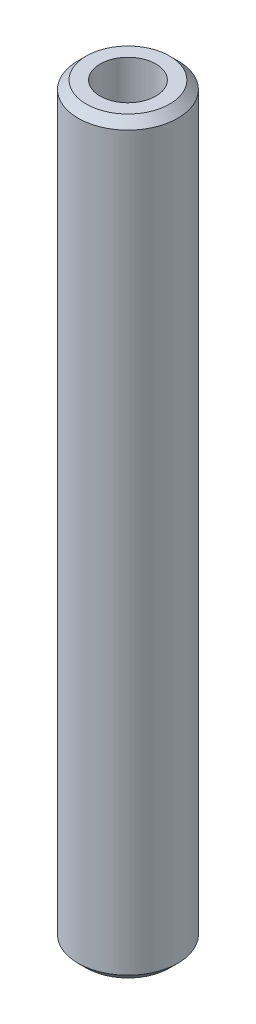
SolidWorks part; units mm, degrees
ref_plane "Front Plane" through (0, 0, 0) normal (0, 0, 1) x (1, 0, 0)
ref_plane "Top Plane" through (0, 0, 0) normal (0, 1, 0) x (1, 0, 0)
ref_plane "Right Plane" through (0, 0, 0) normal (1, 0, 0) x (0, 0, -1)
sketch "Sketch1" plane through (0, 0, 0) normal (0, 1, 0) x (1, 0, 0)
  circle A0 centre (0, 0) radius 35
  dimension "SHAFT_OD" = 70
extrude "Boss-Extrude1" add sketch "Sketch1" along normal blind 525.2711
sketch "Sketch2" plane through (0, 0, 0) normal (0, 1, 0) x (1, 0, 0)
  circle A0 centre (0, 0) radius 19.5748
  dimension "BORE_D" = 39.1496
extrude "Cut-Extrude1" cut sketch "Sketch2" along normal through all
chamfer "Chamfer1" distance 5.7364 angle 45 2 edges at (0, 525.2711, 35) (0, 0, 35)
